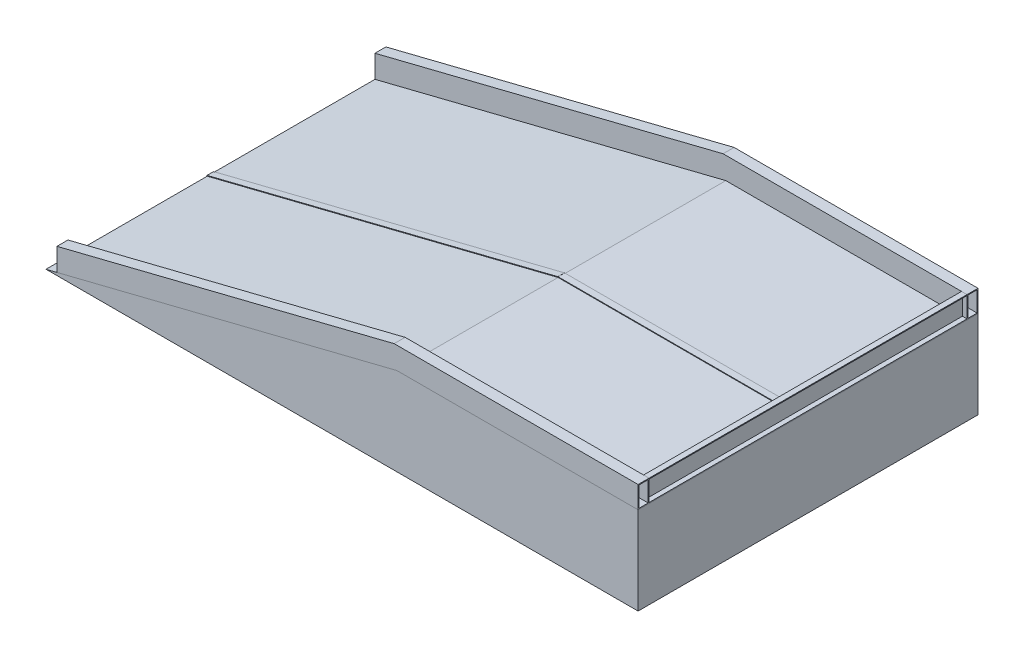
SolidWorks part; units mm, degrees
ref_plane "Front Plane" through (0, 0, 0) normal (0, 0, 1) x (1, 0, 0)
ref_plane "Top Plane" through (0, 0, 0) normal (0, 1, 0) x (1, 0, 0)
ref_plane "Right Plane" through (0, 0, 0) normal (1, 0, 0) x (0, 0, -1)
sketch "Sketch1" plane through (0, 0, 0) normal (0, 0, 1) x (1, 0, 0)
  line L0 (-2700, 0) -> (0, 0)
  line L1 (-2700, 0) -> (-1100, 400)
  line L2 (-1100, 400) -> (0, 400)
  line L4 (0, 0) -> (0, 400)
  dimension "D1" = 1600
  dimension "D2" = 2700
  dimension "D3" = 400
extrude "Boss-Extrude1" add sketch "Sketch1" along normal blind 775 and the other way blind 775
sketch "Sketch3" plane through (0, 0, 775) normal (0, 0, 1) x (1, 0, 0)
  line L0 (-2650, 12.5) -> (-2650, 115.5776)
  line L1 (-2650, 115.5776) -> (-1112.3106, 500)
  line L3 (-1100, 400) -> (-2650, 12.5)
  line L4 (-1100, 400) -> (-2700, 0) construction
  line L5 (0, 0) -> (0, 400) construction
  line L6 (-1150, 500) -> (0, 500)
  line L8 (-1150, 400) -> (0, 400)
  line L9 (0, 500) -> (0, 400)
  line L10 (0, 400) -> (-1100, 400) construction
  line L11 (-1150, 500) -> (-1112.3106, 500)
  line M9 (-1100, 400) -> (-2700, 0)
  line M12 (0, 400) -> (-1100, 400)
  dimension "D1" = 100
  dimension "D2" = 0
  dimension "D3" = 0
  dimension "D4" = 50
  dimension "D5" = 100
  dimension "D7" = 0
  dimension "D8" = 0
extrude "Boss-Extrude2" add sketch "Sketch3" against normal blind 50 separate body contours L6 L11 L1 L0 L9 M9 M12 region at (-2623.0553, 64.0388, 775)
shell "Shell1" thickness 4 removed face at (0, 450, 750) removed face at (-2650, 64.0388, 750)
sketch "Sketch4" plane through (0, 0, -775) normal (0, 0, -1) x (-1, 0, 0)
  line L0 (1100, 400) -> (2650, 12.5) construction
  line L1 (0, 400) -> (1100, 400) construction
  line L3 (2650, 115.5776) -> (1112.3106, 500) construction
  line L5 (0, 500) -> (0, 400) construction
  line L6 (1100, 400) -> (2650, 12.5)
  line L7 (0, 400) -> (1100, 400)
  line L9 (2650, 115.5776) -> (1112.3106, 500)
  line L10 (1112.3106, 500) -> (0, 500)
  line L11 (0, 500) -> (0, 400)
  line L12 (2700, 0) -> (2700, 103.0776)
  line L13 (2650, 115.5776) -> (2700, 103.0776)
  line L14 (2650, 12.5) -> (2700, 0)
extrude "Boss-Extrude3" add sketch "Sketch4" against normal blind 50 separate body
shell "Shell2" thickness 4 removed face at (-2700, 51.5388, -750) removed face at (0, 450, -750)
sketch "Sketch5" plane through (0, 400, 0) normal (0, 1, 0) x (1, 0, 0)
  line L0 (0, 775) -> (0, -775) construction
  line L1 (-25, 725) -> (0, 725)
  line L2 (-25, 725) -> (-25, -725)
  line L3 (-25, -725) -> (0, -725)
  line L4 (0, 725) -> (0, -725)
  line L5 (-1112.3106, 725) -> (0, 725) construction
  line L7 (-1100, -725) -> (-2650, -725) construction
  dimension "D1" = 25
  dimension "D2" = 0
  dimension "D3" = 0
extrude "Boss-Extrude4" add sketch "Sketch5" along normal blind 100 separate body
shell "Shell3" thickness 4 removed face at (-12.5, 450, -725) removed face at (0, 450, 0) removed face at (-12.5, 450, 725)
sketch "Sketch7" plane through (0, 400, 0) normal (0, 1, 0) x (1, 0, 0)
  line L0 (-25, 725) -> (-25, -725) construction
  line L1 (-1100, -10) -> (-25, -10)
  line L2 (-1100, -10) -> (-1100, -40)
  line L3 (-1100, -40) -> (-25, -40)
  line L4 (-25, -10) -> (-25, -40)
  line L5 (-1100, 775) -> (-1100, -775) construction
  line L6 (-1112.3106, 725) -> (0, 725) construction
  dimension "D1" = 30
  dimension "D2" = 0
  dimension "D3" = 0
  dimension "D4" = 735
extrude "Boss-Extrude5" add sketch "Sketch7" along normal blind 3 separate body
sketch "Sketch8" plane through (-158.8235, 635.2941, 0) normal (-0.2425, 0.9701, 0) x (0.9701, 0.2425, 0)
  line L0 (73.4883, -10) -> (-969.4149, -10) construction
  line L1 (-2619.3848, -10) -> (-970.1425, -10)
  line L2 (-2619.3848, -10) -> (-2619.3848, -40)
  line L3 (-2619.3848, -40) -> (-970.1425, -40)
  line L4 (-970.1425, -10) -> (-970.1425, -40)
  line L5 (-970.1425, 775) -> (-970.1425, -775) construction
  line L6 (-2619.3848, 775) -> (-2619.3848, -775) construction
  point P8 (-2619.3848, -25)
  dimension "D1" = 30
  dimension "D2" = 0
  dimension "D3" = 0
  dimension "D4" = 0
extrude "Boss-Extrude6" add sketch "Sketch8" along normal blind 3 separate body
